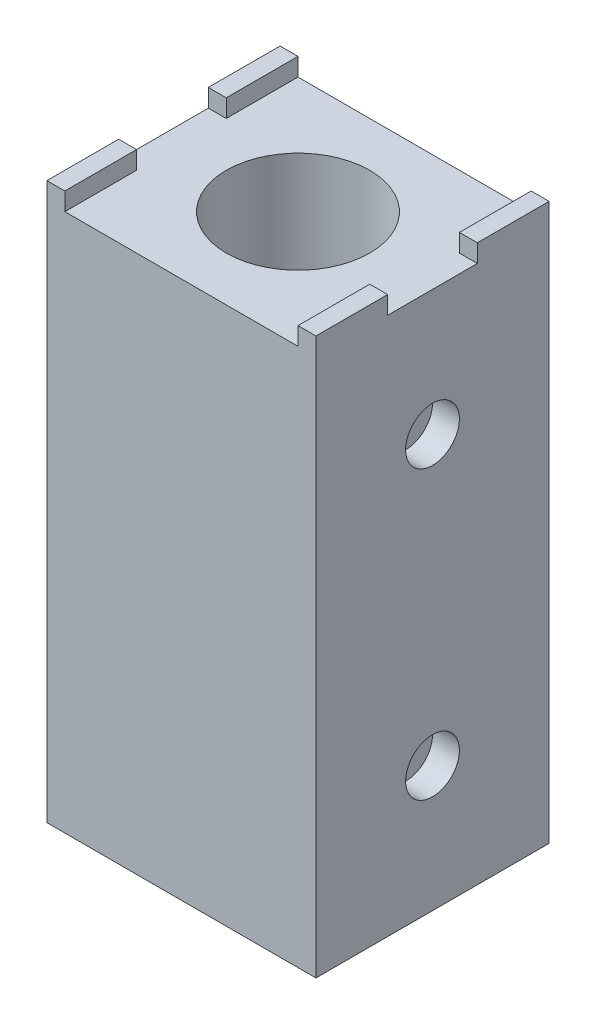
SolidWorks part; units mm, degrees
ref_plane "Front Plane" through (0, 0, 0) normal (0, 0, 1) x (1, 0, 0)
ref_plane "Top Plane" through (0, 0, 0) normal (0, 1, 0) x (1, 0, 0)
ref_plane "Right Plane" through (0, 0, 0) normal (1, 0, 0) x (0, 0, -1)
sketch "Sketch2" plane through (0, 0, 0) normal (0, 1, 0) x (1, 0, 0)
  line L1 (-7.5, 6.5) -> (7.5, 6.5)
  line L2 (-7.5, 6.5) -> (-7.5, -6.5)
  line L3 (-7.5, -6.5) -> (7.5, -6.5)
  line L4 (7.5, 6.5) -> (7.5, -6.5)
  line L5 (-7.5, 6.5) -> (7.5, -6.5) construction
  line L6 (-7.5, -6.5) -> (7.5, 6.5) construction
  point P0 (0, 0)
  dimension "D1" = 13
  dimension "D2" = 15
extrude "Boss-Extrude1" add sketch "Sketch2" along normal blind 30
sketch "Sketch3" plane through (0, 30, 0) normal (0, 1, 0) x (1, 0, 0)
  line L1 (7.5, 6.5) -> (6.5, 6.5)
  line L2 (7.5, 6.5) -> (7.5, 2.5)
  line L3 (7.5, 2.5) -> (6.5, 2.5)
  line L4 (6.5, 6.5) -> (6.5, 2.5)
  line L5 (7.5, -6.5) -> (6.5, -6.5)
  line L6 (7.5, -6.5) -> (7.5, -2.5)
  line L7 (7.5, -2.5) -> (6.5, -2.5)
  line L8 (6.5, -6.5) -> (6.5, -2.5)
  line L9 (-7.5, -6.5) -> (-6.5, -6.5)
  line L10 (-7.5, -6.5) -> (-7.5, -2.5)
  line L11 (-7.5, -2.5) -> (-6.5, -2.5)
  line L12 (-6.5, -6.5) -> (-6.5, -2.5)
  line L13 (-7.5, 6.5) -> (-6.5, 6.5)
  line L14 (-7.5, 6.5) -> (-7.5, 2.5)
  line L15 (-7.5, 2.5) -> (-6.5, 2.5)
  line L16 (-6.5, 6.5) -> (-6.5, 2.5)
  dimension "D1" = 4
  dimension "D2" = 4
  dimension "D3" = 4
  dimension "D4" = 4
  dimension "D5" = 1
  dimension "D6" = 1
  dimension "D7" = 1
  dimension "D8" = 1
extrude "Boss-Extrude2" add sketch "Sketch3" along normal blind 1
sketch "Sketch4" plane through (0, 30, 0) normal (0, 1, 0) x (1, 0, 0)
  circle A0 centre (0, 0) radius 4
  dimension "D1" = 8
extrude "Cut-Extrude3" cut sketch "Sketch4" against normal blind 22
sketch "Sketch5" plane through (0, 8, 0) normal (0, 1, 0) x (1, 0, 0)
  circle A0 centre (0, 0) radius 2
  dimension "D1" = 4
extrude "Cut-Extrude4" cut sketch "Sketch5" against normal blind 5
sketch "Sketch7" plane through (0, 3, 0) normal (0, 1, 0) x (1, 0, 0)
  circle A0 centre (0, 0) radius 1.5
  dimension "D1" = 3
extrude "Cut-Extrude5" cut sketch "Sketch7" against normal through all
fillet "Fillet4" radius 3 1 edges at (0, 8, 2) first distance on face at (0, 8, 2)
fillet "Fillet5" radius 3 1 edges at (0, 3, 1.5) first distance on face at (0, 3, 1.5)
hole_wizard "Ø8.0 (3) Diameter Hole1" positions "3DSketch4" profile "Sketch10" hole size "Ø8.0" standard "ANSI Metric"
sketch3d "3DSketch4"
  line L0 (7.5, 31, -6.5) -> (7.5, 0, -6.5) construction
  line L1 (7.5, 0, 6.5) -> (7.5, 0, -6.5) construction
  line L2 (7.5, 30, 2.5) -> (7.5, 30, -2.5) construction
  point P0 (7.5, 7, 0)
  point P2 (7.5, 23, 0)
  dimension "D1" = 6.5
  dimension "D2" = 7
  dimension "D3" = 7
  dimension "D4" = 6.5
sketch "Sketch10" plane through (7.5, 7, 0) normal (0, 1, 0) x (0, 0, -1)
  line L0 (0, 0) -> (0, 1.5)
  line L1 (0, 1.5) -> (1.5, 1.5)
  line L2 (1.5, 1.5) -> (1.5, 0)
  line L5 (1.5, 0) -> (0, 0)
  line L10 (0, 1.5) -> (-1.5, 1.5) construction
  line L11 (0, -6.35) -> (0, 107.95) construction
  dimension "Hole Dia." = 3
  dimension "Hole Depth" = 1.5
  dimension "Drill Angle" = 180
sketch "Sketch11" plane through (7.5, 0, 0) normal (1, 0, 0) x (0, 0, -1)
  line L0 (0, 24.5) -> (0, 21.5) construction
  line L1 (0, 8.5) -> (0, 5.5) construction
  circle A0 centre (0, 23) radius 1.5 construction
  circle A1 centre (0, 23) radius 1.5 construction
  circle A2 centre (0, 7) radius 1.5 construction
  circle A3 centre (0, 7) radius 1.5 construction
